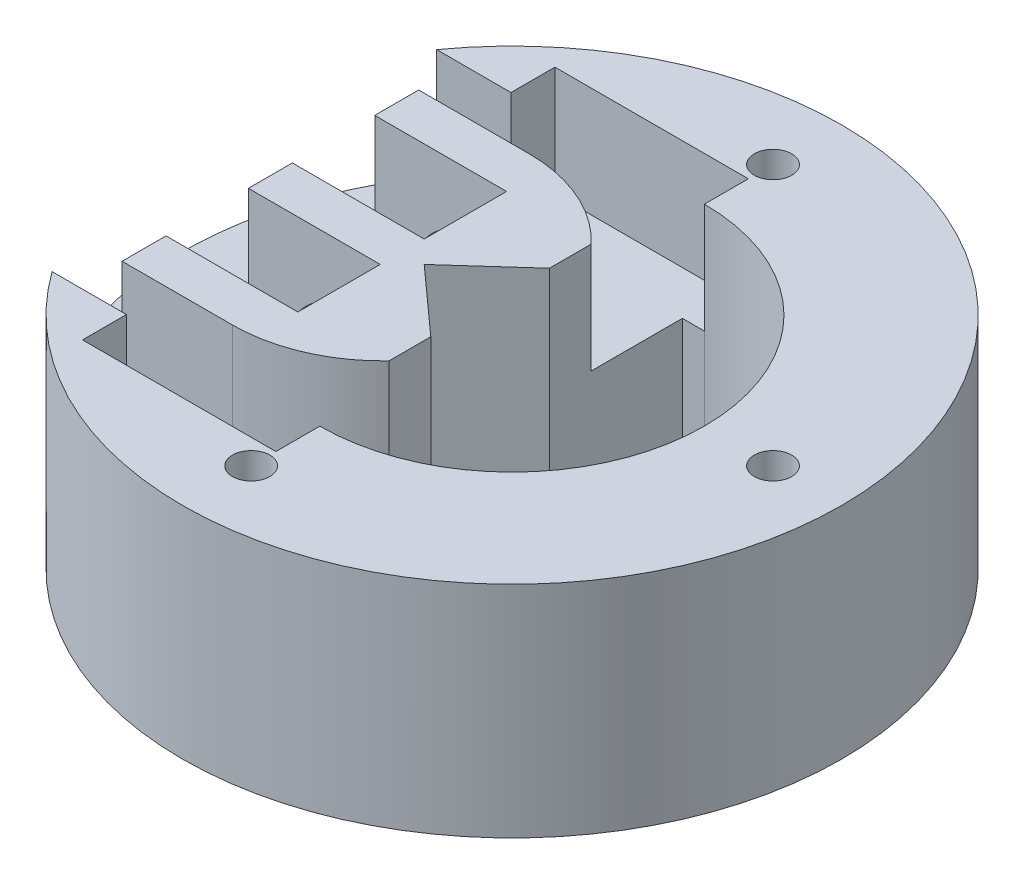
SolidWorks part; units mm, degrees
note: The reader was unsure of these and kept them because the rebuilt part matched: shared geometry of "Sketch3<3>".
ref_plane "Front Plane" through (0, 0, 0) normal (0, 0, 1) x (1, 0, 0)
ref_plane "Top Plane" through (0, 0, 0) normal (0, 1, 0) x (1, 0, 0)
ref_plane "Right Plane" through (0, 0, 0) normal (1, 0, 0) x (0, 0, -1)
sketch "Sketch2" plane through (0, 0, 0) normal (0, 1, 0) x (1, 0, 0)
  circle A0 centre (0, 0) radius 30
  dimension "D1" = 60
extrude "Boss-Extrude1" add sketch "Sketch2" along normal blind 20
sketch "Sketch3" plane through (0, 20, 0) normal (0, 1, 0) x (1, 0, 0)
  line L0 (-24.367, 17.5) -> (-17.6, 17.5)
  line L1 (-17.6, 17.5) -> (-17.6, 21.5)
  line L2 (-17.6, 21.5) -> (0, 21.5)
  line L3 (0, 21.5) -> (0, 17.5)
  line L4 (0, -21.5) -> (0, -17.5)
  line L5 (0, -21.5) -> (-17.6, -21.5)
  line L6 (-17.6, -21.5) -> (-17.6, -17.5)
  line L7 (-17.6, -17.5) -> (-24.367, -17.5)
  line L9 (-11.9664, 13.5) -> (-22, 13.5)
  line L10 (-22, 13.5) -> (-22, 9.5)
  line L11 (-22, 9.5) -> (-10, 9.5)
  line L12 (-10, 9.5) -> (-10, 2)
  line L13 (-10, 2) -> (-22, 2)
  line L14 (-22, 2) -> (-22, -2)
  line L15 (-22, -2) -> (-10, -2)
  line L16 (-10, -2) -> (-10, -9.5)
  line L17 (-10, -9.5) -> (-22, -9.5)
  line L18 (-22, -9.5) -> (-22, -13.5)
  line L22 (-22, -13.5) -> (-11.9664, -13.5)
  line L23 (-2, 5.4) -> (-2, 9.2)
  line L25 (-2, -5.4) -> (-2, -9.2)
  line L28 (-2, -9.2) -> (-2, -17.5)
  line L29 (-2, 9.2) -> (-2, 17.5)
  line L30 (0, 17.5) -> (0, -17.5) construction
  line L31 (-2, 17.5) -> (0, 17.5)
  line L32 (-2, -17.5) -> (0, -17.5)
  line L33 (-2, 5.4) -> (-8, 0)
  line L34 (-8, 0) -> (-2, -5.4)
  circle A0 centre (0, 0) radius 30 construction
  arc A1 (0, 17.5) -> (0, -17.5) centre (0, 0) cw
  arc A2 (-24.367, 17.5) -> (-24.367, -17.5) centre (0, 0) ccw
  arc A4 (0, 5) -> (0, -5) centre (0, 0) ccw construction
  arc A5 (-11.9664, 13.5) -> (-2, 9.2) centre (-11.9664, -0.2) cw
  arc A7 (-11.9664, -13.5) -> (-2, -9.2) centre (-11.9664, 0.2) ccw
  point P35 (-22, 0)
  point P36 (0, 0)
  point P40 (0, 0)
  point P41 (-8.2065, -0.2)
  point P42 (-8.4021, -0.2)
  point P44 (0, 0)
  point P45 (0, 0)
  point P46 (-8.9403, -0.2)
  point P47 (0, 0)
  point P48 (0, 0)
  dimension "D9" = 3.8
  dimension "D7" = 5.4
  dimension "D12" = 5
  dimension "D10" = 13.7
  dimension "D2" = 4
  dimension "D3" = 35
  dimension "D4" = 4
  dimension "D5" = 4
  dimension "D6" = 4
  dimension "D8" = 17.6
  dimension "D11" = 12
  dimension "D13" = 2
  dimension "D14" = 5.4
  dimension "D15" = 8
  dimension "D16" = 20
extrude "Cut-Extrude2" cut sketch "Sketch3" against normal through all
extrude "Cut-Extrude3" cut sketch "Sketch3<3>" against normal blind 10
sketch "Sketch3<3>" plane through (0, 20, 0) normal (0, 1, 0) x (1, 0, 0) same geometry as "Sketch3"
hole_wizard "CBORE for M3 SHCS1" positions "Sketch4" profile "Sketch5" counterbore size "M3" standard "ANSI Metric" end condition through all
sketch "Sketch4" plane through (0, 0, 0) normal (0, -1, 0) x (-1, 0, 0)
  line L4 (-30, 0) -> (-17.5, 0) construction
  line L6 (0, 30) -> (0, 17.5) construction
  line L8 (0, -17.5) -> (0, -30) construction
  circle A0 centre (0, 0) radius 30 construction
  arc A2 (0, 17.5) -> (0, -17.5) centre (0, 0) ccw construction
  point P0 (0, 23.75)
  point P2 (-23.75, 0)
  point P4 (0, -23.75)
  point P28 (-23.75, 0)
  point P38 (0, -23.75)
  point P40 (0, 23.75)
sketch "Sketch5" plane through (0, 0, -23.75) normal (1, 0, 0) x (0, 0, -1)
  line L0 (0, 0) -> (0, 20)
  line L1 (0, 20) -> (1.7, 20)
  line L3 (1.7, 20) -> (1.7, 3)
  line L4 (3.25, 3) -> (1.7, 3)
  line L5 (3.25, 3) -> (3.25, 0.025)
  line L6 (3.25, 0.025) -> (3.275, 0)
  line L7 (3.275, 0) -> (0, 0)
  line L8 (-3.25, 0.025) -> (-3.275, 0) construction
  line L11 (0, -6.35) -> (0, 107.95) construction
  dimension "Thru Hole Dia." = 3.4
  dimension "Thru Hole Depth" = 20
  dimension "C'Bore Dia." = 6.5
  dimension "C'Bore Depth" = 3
  dimension "Near C'Sink Dia." = 6.55
  dimension "Near C'Sink Angle" = 90
sketch "Sketch6" plane through (-10, 0, 0) normal (-1, 0, 0) x (0, 0, 1)
  line L0 (-5.75, 15) -> (5.75, 15) construction
  line L1 (-9.5, 10) -> (-2, 10) construction
  line L2 (2, 10) -> (9.5, 10) construction
  line L3 (-2, 10) -> (-2, 20) construction
  circle A0 centre (-5.75, 15) radius 2.085
  circle A1 centre (5.75, 15) radius 2.085
  point P4 (0, 15)
  point P8 (-5.75, 10)
  point P12 (5.75, 10)
  point P16 (-2, 15)
  dimension "D1" = 4.17
extrude "Boss-Extrude2" add sketch "Sketch6" along normal blind 3
